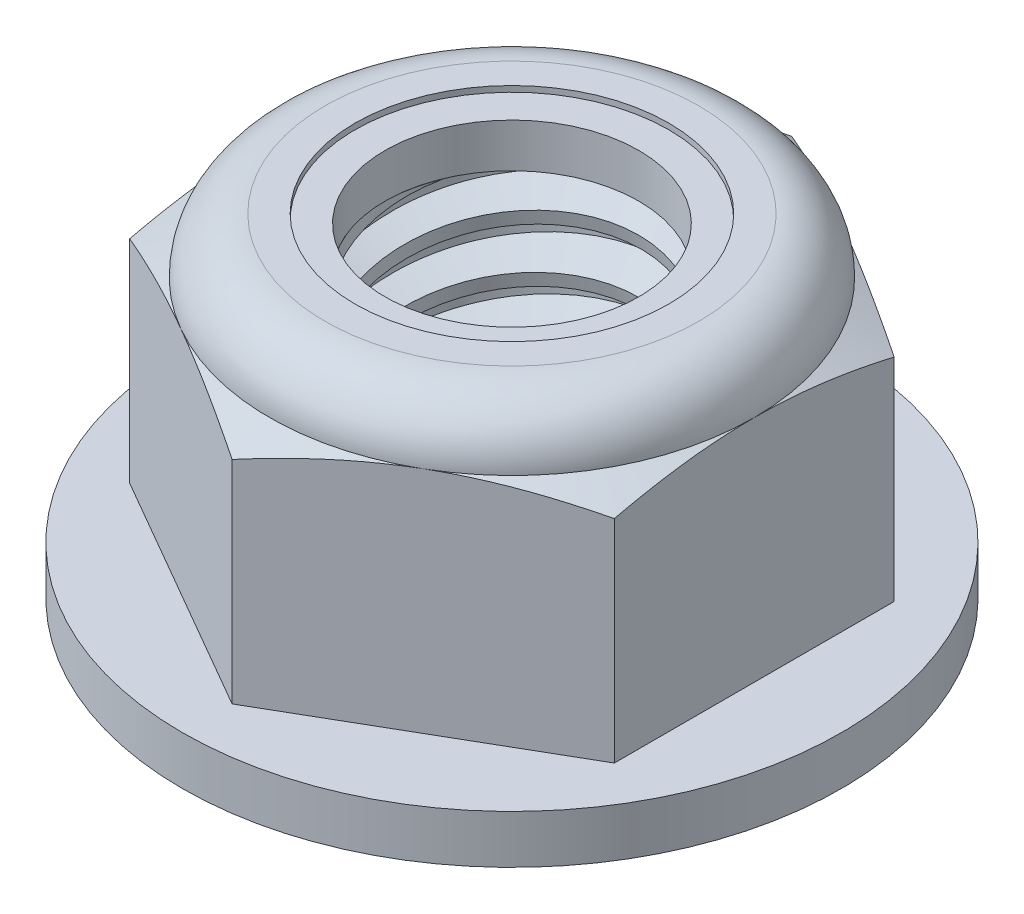
SolidWorks part; units mm, degrees
material "Stainless Steel (ferritic)"
ref_plane "Front" through (0, 0, 0) normal (0, 0, 1) x (1, 0, 0)
ref_plane "Top" through (0, 0, 0) normal (0, 1, 0) x (1, 0, 0)
ref_plane "Right" through (0, 0, 0) normal (1, 0, 0) x (0, 0, -1)
sketch "Sketch1" plane through (0, 0, 0) normal (0, 1, 0) x (1, 0, 0)
  line L1 (0, 7.3323) -> (-6.35, 3.6662)
  line L2 (-6.35, 3.6662) -> (-6.35, -3.6662)
  line L3 (-6.35, -3.6662) -> (0, -7.3323)
  line L4 (0, -7.3323) -> (6.35, -3.6662)
  line L5 (6.35, -3.6662) -> (6.35, 3.6662)
  line L6 (6.35, 3.6662) -> (0, 7.3323)
  circle A0 centre (0, 0) radius 6.35 construction
  dimension "Hex Flats" = 12.7
extrude "Extrude1" add sketch "Sketch1" along normal blind 8.7312
sketch "Sketch8" plane through (0, 0, 0) normal (1, 0, 0) x (0, 0, -1)
  line L0 (0, 0) -> (8.636, 0)
  line L1 (8.636, 0) -> (8.636, 1.27)
  line L2 (8.636, 1.27) -> (0, 1.27)
  line L3 (0, 1.27) -> (0, 0)
  line L4 (0, 0) -> (0, -1.27) construction
  dimension "Flange Height" = 1.27
  dimension "Flange Dia" = 17.272
revolve "Revolve3" add sketch "Sketch8" angle 360 about L4
sketch "Sketch2" plane through (0, 0, 0) normal (1, 0, 0) x (0, 0, -1)
  line L0 (-3.9688, 0) -> (-3.9688, 8.7312) construction
  line L1 (0, 0) -> (3.9688, 0)
  line L2 (0, 0) -> (0, 8.7312)
  line L3 (0, 8.7312) -> (3.9688, 8.7312)
  line L4 (3.9688, 0) -> (3.9688, 8.7312)
  line L5 (-3.6662, 8.7312) -> (3.6662, 8.7312) construction
  line L7 (0, -3.9688) -> (0, 0) construction
  dimension "Thread Dia" = 7.9375
revolve "Revolve1" add sketch "Sketch2" angle 360 about L7
sketch "Sketch3" plane through (0, 0, 0) normal (1, 0, 0) x (0, 0, -1)
  line L0 (3.9688, 8.7312) -> (-3.9688, 8.7312) construction
  line L1 (-3.9688, 8.7312) -> (-3.9688, 7.3201) construction
  line L2 (-3.9688, 7.3201) -> (3.9688, 8.7312) construction
  line L3 (3.9688, 8.7312) -> (3.9996, 8.5576) construction
  line L4 (3.9996, 8.5576) -> (4.2157, 7.3419)
  line L5 (4.2157, 7.3419) -> (3.3866, 7.6424)
  line L6 (3.3866, 7.6424) -> (3.3248, 7.9897)
  line L7 (3.3248, 7.9897) -> (3.9996, 8.5576)
  line L8 (3.3557, 7.8161) -> (4.1077, 7.9498) construction
  line L9 (3.9688, 8.7312) -> (3.9688, 7.9251) construction
  line L10 (3.9688, 7.9251) -> (-3.9688, 6.5139) construction
  line L11 (-3.9688, 6.5139) -> (-3.9688, 7.3201) construction
  line L12 (-0.2688, 8.7312) -> (0.2688, 5.7077) construction
  line L13 (-3.9688, 0) -> (-3.9688, 8.7312) construction
  line L14 (0, 8.7312) -> (3.9688, 8.7312) construction
  line L15 (3.9688, 0) -> (3.9688, 8.7312) construction
  point P13 (0, 7.2195)
  dimension "D1" = 0.1764
  dimension "D2" = 0.3528
  dimension "Thread Pitch" = 1.4111
  dimension "D4" = 60
  dimension "D5" = 1.4111
revolve "Cut-Revolve1" cut sketch "Sketch3" angle 360 about L12
pattern_linear "LPattern1" count 6 spacing 1.4111 along (0, -1, 0) count 2 spacing 1.4111 along (0, 1, 0) of "Cut-Revolve1"
sketch "Sketch4" plane through (0, 0, 0) normal (1, 0, 0) x (0, 0, -1)
  line L0 (0, 8.7312) -> (3.9688, 8.7312)
  line L1 (3.9688, 8.7312) -> (3.3248, 8.431)
  line L2 (3.3248, 8.431) -> (3.3248, 0.3003)
  line L3 (3.3248, 0.3003) -> (3.9688, 0)
  line L4 (3.9688, 0) -> (0, 0)
  line L5 (0, 0) -> (0, 8.7312)
  line L6 (3.9688, 0) -> (3.9688, 8.7312) construction
  line L7 (0, 8.7312) -> (3.9688, 8.7312) construction
  line L8 (0, 0) -> (3.9688, 0) construction
  line L9 (0, 0) -> (0, 8.7312) construction
  line L10 (0, 8.7312) -> (0, 9.4418) construction
  dimension "D1" = 25
revolve "Cut-Revolve2" cut sketch "Sketch4" angle 360 about L10
combine bodies "Combine1" operation type subtract main body 112 bodies to subtract 111
sketch "Sketch5" plane through (0, 0, 0) normal (1, 0, 0) x (0, 0, -1)
  line L0 (8.636, 1.27) -> (0, 1.27) construction
  line L1 (0, 0) -> (8.636, 0) construction
  line L2 (7.3323, 1.27) -> (7.3323, 6.818)
  line L3 (7.3323, 6.818) -> (6.35, 7.276)
  line L4 (4.8948, 8.7312) -> (4.8948, 10.0012)
  line L5 (4.8948, 10.0012) -> (8.6023, 10.0012)
  line L6 (8.6023, 10.0012) -> (8.6023, 1.27)
  line L9 (6.35, 7.276) -> (6.35, 0) construction
  line L13 (7.3323, 1.27) -> (8.6023, 1.27)
  line L15 (0, 0) -> (0, 10.0012) construction
  line L20 (0, 10.0012) -> (4.8948, 10.0012) construction
  line L22 (0, 8.7312) -> (3.9688, 8.7312) construction
  arc A0 (6.35, 7.276) -> (4.8948, 8.7312) centre (4.8948, 7.276) ccw
  dimension "D4" = 1.4552
  dimension "D1" = 1.27
  dimension "D2" = 115
  dimension "D3" = 8.7312
revolve "Cut-Revolve3" cut sketch "Sketch5" angle 360 about L15
sketch "Sketch6" plane through (0, 0, 0) normal (1, 0, 0) x (0, 0, -1)
  line L0 (0, 7.276) -> (6.1976, 7.276)
  line L1 (4.8948, 8.5788) -> (4.1098, 8.5788)
  line L2 (0, 10.0012) -> (0, 7.276)
  line L3 (4.1098, 10.0012) -> (0, 10.0012)
  line L4 (0, 10.0012) -> (4.8948, 10.0012) construction
  line L5 (0, 0) -> (0, 10.0012) construction
  line L6 (0, 10.0012) -> (0, 44.323) construction
  line L7 (4.1098, 8.5788) -> (4.1098, 10.0012)
  line L8 (4.8948, 8.7312) -> (4.8948, 8.5788) construction
  line L9 (4.1098, 8.5788) -> (3.3248, 8.5788) construction
  line L10 (3.3248, 8.5788) -> (3.3248, 8.431) construction
  arc A0 (6.1976, 7.276) -> (4.8948, 8.5788) centre (4.8948, 7.276) ccw
  arc A1 (6.35, 7.276) -> (4.8948, 8.7312) centre (4.8948, 7.276) ccw construction
  dimension "D1" = 0.1524
revolve "Cut-Revolve4" cut sketch "Sketch6" angle 360 about L6
sketch "Sketch7" plane through (0, 0, 0) normal (1, 0, 0) x (0, 0, -1)
  line L0 (3.3248, 7.3522) -> (6.119, 7.3522)
  line L1 (4.8948, 8.5026) -> (3.3248, 8.5026)
  line L2 (3.3248, 8.5026) -> (3.3248, 7.3522)
  line L3 (3.3248, 7.3522) -> (0, 7.3522) construction
  line L4 (0, 7.3522) -> (0, 8.5026) construction
  line L5 (0, 8.5026) -> (3.3248, 8.5026) construction
  line L6 (3.3248, 7.3522) -> (3.3248, 7.276) construction
  line L7 (0, 7.276) -> (6.1976, 7.276) construction
  line L8 (4.8948, 8.5026) -> (4.8948, 8.5788) construction
  arc A0 (6.119, 7.3522) -> (4.8948, 8.5026) centre (4.8948, 7.276) ccw
  arc A2 (6.1976, 7.276) -> (4.8948, 8.5788) centre (4.8948, 7.276) ccw construction
  dimension "D1" = 0.0762
revolve "Revolve2" add sketch "Sketch7" angle 360 about L4
equation "\"D1@Sketch3\"=\"Thread Pitch@Sketch3\"/8"
equation "\"D2@Sketch3\"=\"Thread Pitch@Sketch3\"/4"
equation "\"D5@Sketch3\"=\"Thread Pitch@Sketch3\""
equation "\"D4@LPattern1\"=\"Thread Pitch@Sketch3\""
equation "\"D3@LPattern1\"=\"Thread Pitch@Sketch3\""
equation "\"D1@LPattern1\"=\"Height@Extrude1\"/\"Thread Pitch@Sketch3\""
equation "\"D4@Sketch5\"=\"Height@Extrude1\"/6"
